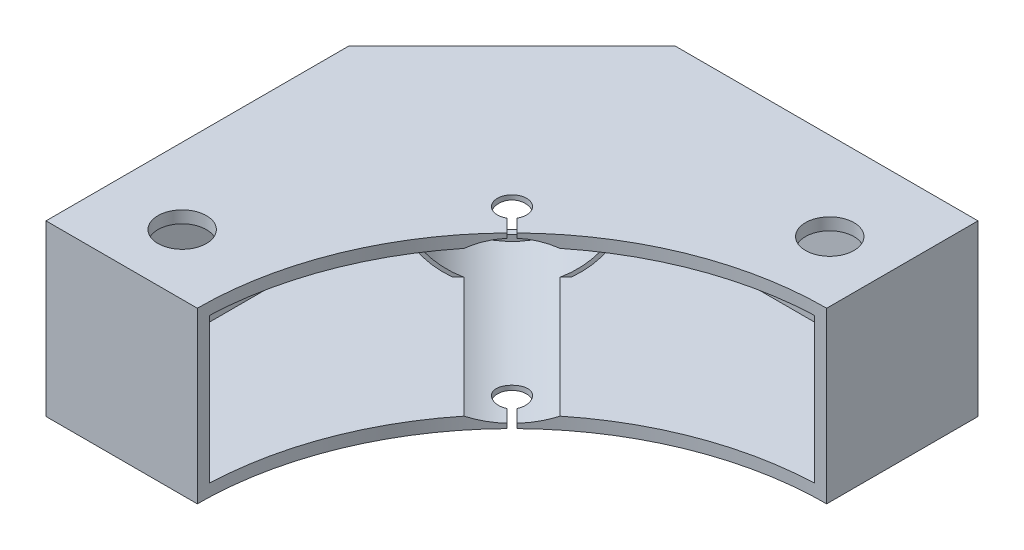
SolidWorks part; units mm, degrees
ref_plane "Front Plane" through (0, 0, 0) normal (0, 0, 1) x (1, 0, 0)
ref_plane "Top Plane" through (0, 0, 0) normal (0, 1, 0) x (1, 0, 0)
ref_plane "Right Plane" through (0, 0, 0) normal (1, 0, 0) x (0, 0, -1)
sketch "Sketch1" plane through (0, 0, 0) normal (0, 1, 0) x (1, 0, 0)
  line L0 (0, 0) -> (0, 50)
  line L1 (0, 0) -> (25, 0)
  line L2 (27, 77) -> (0, 50)
  line L3 (27, 77) -> (77, 77)
  line L4 (77, 77) -> (77, 52)
  line L5 (40.6572, 37.1914) -> (39.8086, 36.3428) construction
  line L6 (39.8086, 36.3428) -> (37.6873, 38.4642)
  line L7 (40.6572, 37.1914) -> (38.5358, 39.3127)
  line L8 (77, 52) -> (77, 0) construction
  line L9 (25, 0) -> (77, 0) construction
  arc A0 (39.8086, 36.3428) -> (25, 0) centre (77, 0) ccw
  arc A1 (40.6572, 37.1914) -> (77, 52) centre (77, 0) cw
  arc A2 (37.6873, 38.4642) -> (38.5358, 39.3127) centre (36.4684, 40.5316) cw
  dimension "D2" = 52
  dimension "D11" = 2.4
  dimension "D5" = 135
  dimension "D6" = 1.2
  dimension "D9" = 3
  dimension "D7" = 25
extrude "Boss-Extrude1" add sketch "Sketch1" along normal blind 28
shell "Shell1" thickness 2 removed face at (58.1033, 14, -46.3757) removed face at (30.6243, 14, -18.8967)
ref_plane "Plane3" through (0, 14, 0) normal (0, 1, 0) x (1, 0, 0)
sketch "Sketch7" plane through (0, 14, 0) normal (0, 1, 0) x (1, 0, 0)
  line L0 (0, 0) -> (0, 50)
  line L1 (0, 0) -> (25, 0)
  line L2 (25, 75) -> (0, 50)
  line L3 (25, 75) -> (75, 75)
  line L4 (75, 75) -> (75, 50)
  line L5 (40.431, 36.1246) -> (38.8754, 34.569) construction
  line L6 (38.8754, 34.569) -> (36.7541, 36.6903)
  line L7 (40.431, 36.1246) -> (38.3097, 38.2459)
  line L8 (75, 50) -> (75, 0) construction
  line L9 (25, 0) -> (75, 0) construction
  arc A0 (38.8754, 34.569) -> (25, 0) centre (75, 0) ccw
  arc A1 (40.431, 36.1246) -> (75, 50) centre (75, 0) cw
  arc A2 (36.7541, 36.6903) -> (38.3097, 38.2459) centre (36.1847, 38.8153) cw
  dimension "D5" = 135
  dimension "D2" = 50
  dimension "D11" = 2.2
  dimension "D6" = 2.2
  dimension "D7" = 25
  dimension "D9" = 3
sketch "Sketch9" plane through (0, 14, 0) normal (0, 1, 0) x (1, 0, 0)
  circle A0 centre (36.1847, 38.8153) radius 6.4
  dimension "D1" = 12.8
extrude "Cut-Extrude1" cut sketch "Sketch9" against normal blind 12 and the other way blind 12
sketch "Sketch11" plane through (-25, 0, -25) normal (-0.7071, 0, -0.7071) x (-0.7071, 0, 0.7071)
  line L0 (-73.5391, 28) -> (-35.3553, 0) construction
  circle A0 centre (-54.4472, 14) radius 13.85
  point P8 (-54.4472, 14)
  dimension "D1" = 27.7
ref_plane "Plane4" through (0, 28, 0) normal (0, 1, 0) x (1, 0, 0)
sketch "Sketch12" plane through (0, 28, 0) normal (0, 1, 0) x (1, 0, 0)
  line L2 (77, 52) -> (77, 77) construction
  line L5 (40.431, 36.1246) -> (38.8754, 34.569) construction
  line L8 (75, 50) -> (75, 0) construction
  line L9 (25, 0) -> (75, 0) construction
  line L10 (77, 62.5) -> (67, 62.5) construction
  line L11 (12.5, 0) -> (12.5, 10) construction
  circle A3 centre (67, 62.5) radius 4
  circle A4 centre (12.5, 10) radius 4
  point P0 (0, 0)
  dimension "D3" = 8
  dimension "D10" = 8
  dimension "D6" = 2.2
  dimension "D4" = 10
extrude "Cut-Extrude3" cut sketch "Sketch12" against normal blind 2
extrude "Boss-Extrude2" add sketch "Sketch11" along normal blind 0.0001 and the other way blind 10
sketch "Sketch13" plane through (-17.9289, 0, -17.9289) normal (0.7071, 0, 0.7071) x (0.7071, 0, -0.7071)
  line L0 (61.3626, 2) -> (47.5318, 26) construction
  circle A0 centre (54.4472, 14) radius 13.25
  dimension "D1" = 26.5
extrude "Cut-Extrude4" cut sketch "Sketch13" against normal blind 9 and the other way blind 35
sketch "Sketch15" plane through (-25, 0, -25) normal (-0.7071, 0, -0.7071) x (-0.7071, 0, 0.7071)
  line L0 (-73.5391, 0) -> (-35.3553, 28) construction
  circle A0 centre (-54.4472, 14) radius 12.25
  dimension "D1" = 24.5
extrude "Cut-Extrude5" cut sketch "Sketch15" against normal blind 10 and the other way blind 10
equation "\"innerRadius\"= 52mm"
equation "\"addedDimension\"= 25mm"
equation "\"D2@Sketch1\"=\"innerRadius\""
equation "\"thinConnectorWidth\"= 1.2mm"
equation "\"D6@Sketch1\"=\"thinConnectorWidth\""
equation "\"D9@Sketch1\"=\"thinConnectorLength\""
equation "\"thinConnectorLength\"= 3mm"
equation "\"connectorCircleRadius\"= 2.4mm"
equation "\"D11@Sketch1\"=\"connectorCircleRadius\""
equation "\"D7@Sketch1\"=\"addedDimension\""
equation "\"shellWidth\"= 2mm"
equation "\"D1@Shell1\"=\"shellWidth\""
equation "\"extrusionHeight\"= 28mm"
equation "\"D1@Boss-Extrude1\"=\"extrusionHeight\""
equation "\"D1@Sketch9\"=2*(\"connectorCircleRadius\"+\"thinConnectorLength\") + \"shellWidth\""
equation "\"D2@Cut-Extrude1\"=\"extrusionHeight\"/2 - \"shellWidth\""
equation "\"D1@Cut-Extrude1\"=\"extrusionHeight\"/2-\"shellWidth\""
equation "\"magnetHoleDiam\"= 26.5mm"
equation "\"D1@Sketch11\"=\"magnetHoleDiam\" + 1.2"
equation "\"throughHoleRadius\"= 4mm"
equation "\"D3@Sketch12\"=\"throughHoleRadius\"*2"
equation "\"D10@Sketch12\"=\"throughHoleRadius\"*2"
equation "\"throughHoleDistanceFromEdge\"= 10mm"
equation "\"D1@Cut-Extrude3\"=\"shellWidth\""
equation "\"D1@Sketch13\"=\"magnetHoleDiam\""
equation "\"D1@Sketch15\"=\"magnetHoleDiam\"-2"
